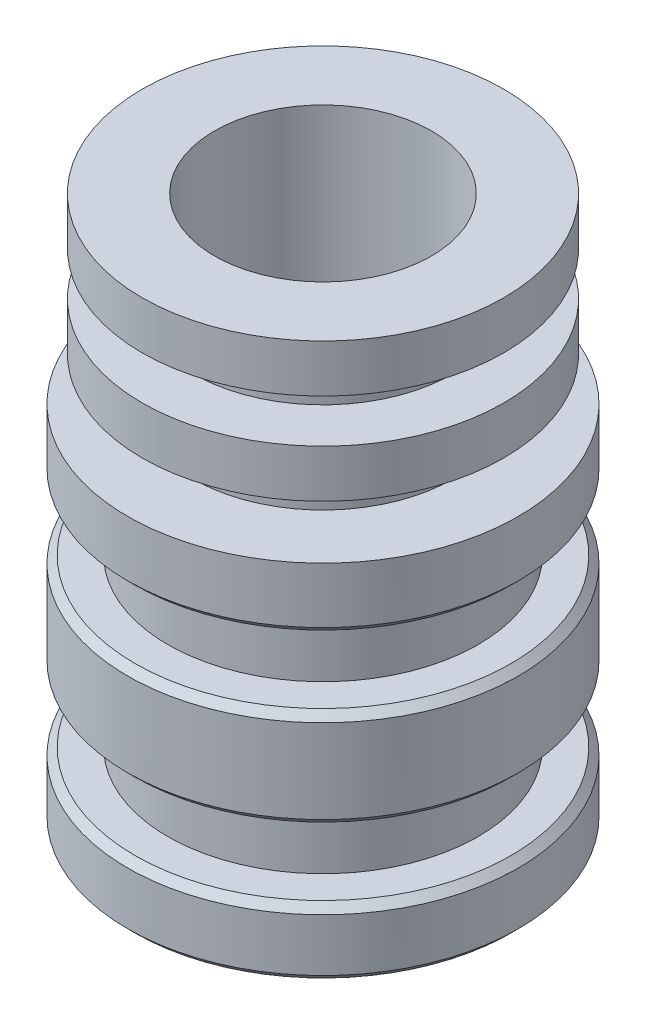
SolidWorks part; units mm, degrees
material "AISI 316 Barre d'acier inoxydable recuit (SS)"
ref_plane "Plan de face" through (0, 0, 0) normal (0, 0, 1) x (1, 0, 0)
ref_plane "Plan de dessus" through (0, 0, 0) normal (0, 1, 0) x (1, 0, 0)
ref_plane "Plan de droite" through (0, 0, 0) normal (1, 0, 0) x (0, 0, -1)
sketch "Esquisse1" plane through (0, 0, 0) normal (0, 0, 1) x (1, 0, 0)
  line L0 (0, -29.1154) -> (0, 30.7029) construction
  line L4 (-2, 15.34) -> (-2, -5.66) construction
  line L5 (-2, -5.66) -> (0, -5.66) construction
  line L9 (0, 0) -> (-13.5, 0)
  line L10 (-13.5, 0) -> (-13.5, 25.2) construction
  line L11 (-2, 15.34) -> (-7.5, 20.84) construction
  line L13 (-12.5, 29.0574) -> (-12.5, 31.5) construction
  line L18 (-12.5, 31.5) -> (-12.5, 28.2)
  line L19 (-12.5, 28.2) -> (-9, 28.2)
  line L20 (-9, 28.2) -> (-9, 25.2)
  line L29 (-9, 25.2) -> (-12.5, 25.2)
  line L33 (-13.5, 25.2) -> (-12.5, 25.2)
  line L35 (-13.5, 25.2) -> (-13.5, 20.84)
  line L36 (-13.5, 16.14) -> (-13.5, 9.34)
  line L37 (-13.5, 4.64) -> (-13.5, 0)
  line L39 (-2, 15.34) -> (-2, -5.66) construction
  line L42 (-7.5, 20.84) -> (-7.5, 8)
  line L43 (-7.5, 8) -> (0, 8)
  line L44 (-13.5, 20.84) -> (-10.73, 20.84)
  line L45 (-10.73, 20.84) -> (-10.73, 16.14)
  line L46 (-10.73, 16.14) -> (-13.5, 16.14)
  line L47 (-13.5, 9.34) -> (-10.73, 9.34)
  line L48 (-10.73, 9.34) -> (-10.73, 4.64)
  line L49 (-10.73, 4.64) -> (-13.5, 4.64)
  line L50 (0, 8) -> (0, 0)
  line L51 (-12.5, 31.5) -> (-9, 31.5)
  line L52 (-9, 31.5) -> (-9, 34.5)
  line L53 (-9, 34.5) -> (-12.5, 34.5)
  line L54 (-12.5, 34.5) -> (-12.5, 37.8)
  line L55 (-12.5, 37.8) -> (-7.5, 37.8)
  line L56 (-7.5, 37.8) -> (-7.5, 20.84)
  point P3 (-13, 25.2)
  dimension "D5" = 4.7
  dimension "D12" = 25.2
  dimension "D7" = 10.73
  dimension "D1" = 2
  dimension "D2" = 13.5
  dimension "D3" = 7.5
  dimension "D4" = 1
  dimension "D6" = 6.8
  dimension "D8" = 4.36
  dimension "D9" = 4.64
  dimension "D10" = 3
  dimension "45" = 45
  dimension "D11" = 8
  dimension "D13" = 21
  dimension "D14" = 9
  dimension "D15" = 3.5
  dimension "D16" = 12.5
  dimension "D17" = 3.3
revolve "Révolution1" add sketch "Esquisse1" angle 360 about L0
sketch "Esquisse4" plane through (0, 0, 0) normal (0, -1, 0) x (1, 0, 0)
  circle A0 centre (0, 0) radius 2
  dimension "D1" = 4
extrude "Enlèv. mat.-Extru.3" cut sketch "Esquisse4" against normal through all
chamfer "Chanfrein4" distance 0.5 angle 45 2 edges at (0, 8, -2) (0, 0, -2)
chamfer "Chanfrein3" distance 0.5 angle 45 5 edges at (0, 0, -13.5) (0, 20.84, -13.5) (0, 16.14, -13.5) (0, 9.34, -13.5) (0, 4.64, -13.5)
equation "\"1à.00mm\"=12"
